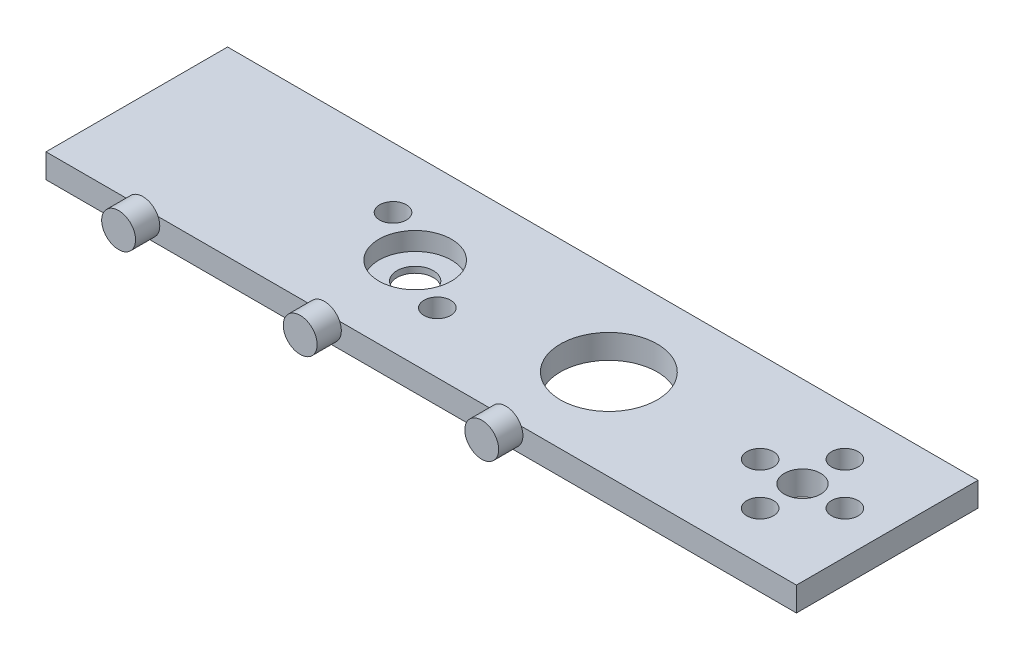
SolidWorks part; units mm, degrees
ref_plane "前视基准面" through (0, 0, 0) normal (0, 0, 1) x (1, 0, 0)
ref_plane "上视基准面" through (0, 0, 0) normal (0, 1, 0) x (1, 0, 0)
ref_plane "右视基准面" through (0, 0, 0) normal (1, 0, 0) x (0, 0, -1)
other "Configuration Table"
sketch "草图1" plane through (0, 0, 0) normal (0, 1, 0) x (1, 0, 0)
  line L0 (-31, 7.5) -> (31, 7.5)
  line L1 (31, 7.5) -> (31, -7.5)
  line L2 (31, -7.5) -> (-31, -7.5)
  line L3 (-31, -7.5) -> (-31, 7.5)
  line L4 (-31, 0) -> (31, 0) construction
  line L5 (-12.3301, -2.5) -> (-3.6699, 2.5) construction
  line L6 (-12.8083, -5.95) -> (-3.1917, -5.95) construction
  line L7 (-12.8083, 5.95) -> (-3.1917, 5.95) construction
  line L8 (-8, 7.5) -> (-8, -7.5) construction
  circle A0 centre (-8, 0) radius 1.5
  circle A1 centre (-3.6699, 2.5) radius 1.1
  circle A3 centre (-12.3301, -2.5) radius 1.1
  arc A4 (-12.8083, 5.95) -> (-12.8083, -5.95) centre (-8, 0) ccw construction
  circle A5 centre (8, 0) radius 4
  arc A6 (-3.1917, -5.95) -> (-3.1917, 5.95) centre (-8, 0) ccw construction
  circle A7 centre (24, 0) radius 1.5
  circle A8 centre (24, 0) radius 3.5 construction
  circle A9 centre (27.5, 0) radius 1.1
  circle A10 centre (24, -3.5) radius 1.1
  circle A11 centre (20.5, 0) radius 1.1
  circle A12 centre (24, 3.5) radius 1.1
  circle A13 centre (-12.3301, 2.5) radius 1.1
  circle A14 centre (-3.6699, -2.5) radius 1.1
  point P5 (0, 7.5)
  point P7 (-31, 0)
  dimension "D3" = 3
  dimension "D6" = 2.2
  dimension "D9" = 15.3
  dimension "D12" = 8
  dimension "D14" = 3
  dimension "D15" = 7
  dimension "D16" = 2.2
  dimension "D1" = 62
  dimension "D2" = 15
  dimension "D4" = 23
  dimension "D7" = 30
  dimension "D8" = 10
  dimension "D10" = 11.9
  dimension "D11" = 16
  dimension "D13" = 16
  dimension "D5" = 2
  dimension "D17" = 4
extrude "凸台-拉伸1" add sketch "草图1" along normal blind 2 contours L3 L2 L1 L0 A13 A12 A11 A10 A9 A7 A5 A3 A1 A0 A14 | A3 | A1 region at (-0.9082, 0, 0) region at (-3.6699, 0, -2.5) region at (-12.3301, 0, 2.5)
sketch "草图2" plane through (0, 0, 7.5) normal (0, 0, 1) x (1, 0, 0)
  line L0 (-31, 1.4) -> (31, 1.4) construction
  line L1 (-31, 2) -> (-31, 0) construction
  line L3 (31, 0) -> (-31, 0) construction
  circle A0 centre (-23, 1.4) radius 1.4
  circle A1 centre (-8, 1.4) radius 1.4
  circle A2 centre (7, 1.4) radius 1.4
  dimension "D1" = 2.8
  dimension "D2" = 2.8
  dimension "D3" = 2.8
  dimension "D4" = 15
  dimension "D5" = 15
  dimension "D6" = 8
  dimension "D7" = 1.4
extrude "凸台-拉伸2" add sketch "草图2" along normal blind 2
sketch "草图3" plane through (0, 2, 0) normal (0, 1, 0) x (1, 0, 0)
  text T0 "R" font "Microsoft YaHei UI" height 3.5
sketch "草图4" plane through (0, 2, 0) normal (0, 1, 0) x (1, 0, 0)
  circle A0 centre (-8, 0) radius 3
  dimension "D1" = 6
extrude "切除-拉伸1" cut sketch "草图4" against normal blind 1.5
